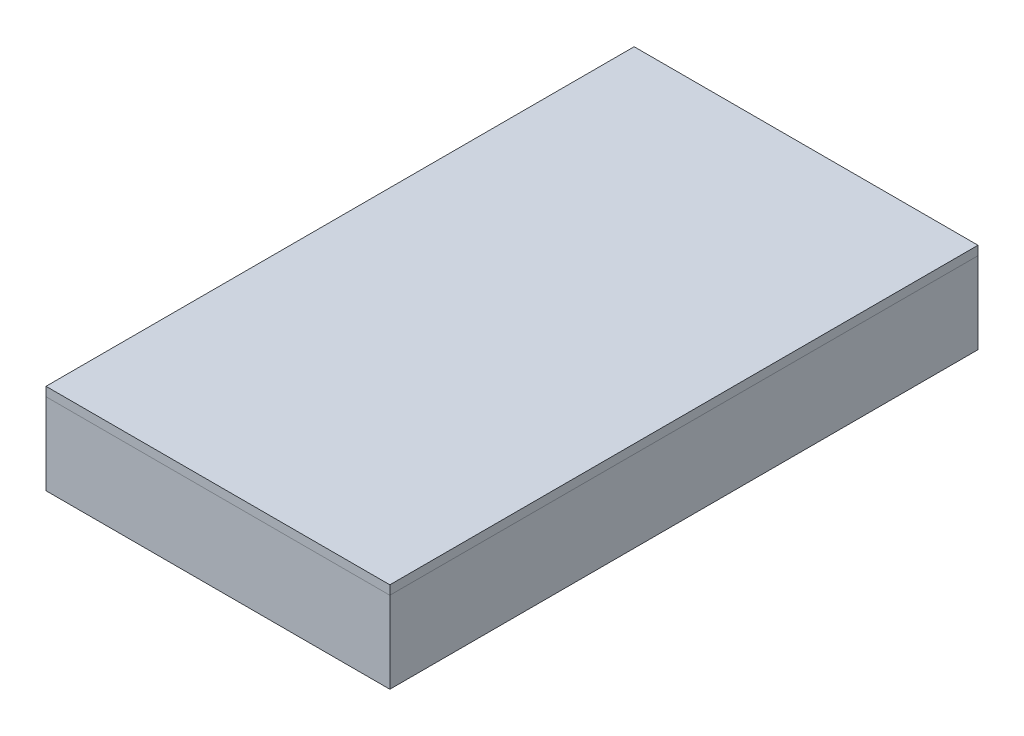
SolidWorks part; units mm, degrees
note: The reader was unsure of these and kept them because the rebuilt part matched: shared geometry of "Sketch3<3>", "Sketch6<3>", "Sketch6<4>".
ref_plane "Front Plane" through (0, 0, 0) normal (0, 0, 1) x (1, 0, 0)
ref_plane "Top Plane" through (0, 0, 0) normal (0, 1, 0) x (1, 0, 0)
ref_plane "Right Plane" through (0, 0, 0) normal (1, 0, 0) x (0, 0, -1)
sketch "Sketch2" plane through (0, 0, 0) normal (0, 1, 0) x (1, 0, 0)
  line L0 (9.3918, 23) -> (12.6392, 30.6504) construction
  line L1 (8.0012, 23) -> (11.3715, 30.9397) construction
  line L2 (-17.4418, -23.5727) -> (-14.5634, 23.4884) construction
  line L3 (14.5634, -23.4884) -> (17.4418, 23.5727) construction
  line L4 (-6.5783, 31) -> (10.4548, 31) construction
  line L5 (-10.4548, -31) -> (6.5783, -31) construction
  line L6 (-6.5783, 23) -> (9.3918, 23) construction
  line L7 (-9.3918, -23) -> (6.5783, -23) construction
  line L8 (-9.3918, -23) -> (-8.2297, -4) construction
  line L9 (9.3333, 22.0431) -> (12.9414, 30.5435) construction
  line L10 (6.5783, -23) -> (9.2488, -30.5411) construction
  line L11 (6.5783, -23) -> (7.7404, -4) construction
  line L12 (-7.7404, 4) -> (8.2297, 4) construction
  line L13 (-8.2297, -4) -> (7.7404, -4) construction
  line L14 (-6.5783, 23) -> (-12.0598, 28.827) construction
  line L15 (8.2297, 4) -> (9.3918, 23) construction
  line L16 (5.2204, -23) -> (8.0078, -30.8713) construction
  line L17 (-7.7404, 4) -> (-6.5783, 23) construction
  line L18 (-9.3918, -23) -> (-18.0557, -31.1502) construction
  line L19 (-11.4496, 29.3459) -> (-5.48, 23) construction
  line L20 (-12.615, 28.2496) -> (-6.6454, 21.9037) construction
  line L21 (-14.9719, -29.3476) -> (-8.2242, -23) construction
  line L22 (-16.0682, -28.1822) -> (-9.3205, -21.8346) construction
  line L23 (6.6283, -22.1826) -> (9.5483, -30.4283) construction
  line L24 (-11.6, 0) -> (-6.2918, 4) construction
  line L25 (-11.6, 0) -> (-6.2918, -4) construction
  line L26 (11.6, 0) -> (6.2918, 4) construction
  line L27 (11.6, 0) -> (6.2918, -4) construction
  line L28 (-7.6819, 4.9559) -> (-12.9293, 1.0017) construction
  line L29 (-12.9293, 1.0017) -> (-15.8061, 3.1696) construction
  line L30 (-16.2126, -3.4758) -> (-12.9293, -1.0017) construction
  line L31 (-12.9293, -1.0017) -> (-8.2615, -4.5192) construction
  line L32 (7.6819, -4.9559) -> (12.9293, -1.0017) construction
  line L33 (12.9293, -1.0017) -> (15.8061, -3.1696) construction
  line L34 (8.2615, 4.5192) -> (12.9293, 1.0017) construction
  line L35 (12.9293, 1.0017) -> (16.2126, 3.4758) construction
  line L36 (-19, -32.5) -> (-19, 32.5) construction
  line L37 (19, -32.5) -> (19, 32.5) construction
  line L38 (-19, 32.5) -> (19, 32.5) construction
  line L39 (-19, -32.5) -> (19, -32.5) construction
  line L40 (-16.8257, -13.5) -> (15.1743, -13.5) construction
  line L41 (-15.1743, 13.5) -> (16.8257, 13.5) construction
  line L42 (16.7794, 27) -> (-13.5065, 27) construction
  line L43 (-10.4548, -31) -> (13.8794, -31) construction
  line L44 (13.5065, -27) -> (-16.7794, -27) construction
  line L45 (10.1479, -30.1595) -> (13.8353, 30.1296) construction
  line L46 (-10.1479, 30.1595) -> (-13.8353, -30.1296) construction
  line L47 (-1.896, -31) -> (1.896, 31) construction
  arc A0 (-6.5783, 31) -> (-14.5634, 23.4884) centre (-6.5783, 23) ccw construction
  arc A1 (14.5634, -23.4884) -> (6.5783, -31) centre (6.5783, -23) cw construction
  arc A2 (17.4418, 23.5727) -> (10.4548, 31) centre (10.4548, 24) ccw construction
  arc A3 (-10.4548, -31) -> (-17.4418, -23.5727) centre (-10.4548, -24) cw construction
  point P0 (-16, 0)
  point P3 (-16, 0)
  point P8 (16, 0)
  point P42 (-11.6, 0)
  point P43 (11.6, 0)
  point P67 (7.1594, -13.5)
  point P70 (-7.1594, 13.5)
  point P72 (1.9383, 31)
  point P85 (1.6364, 27)
  point P86 (-12.8182, -13.5)
  point P87 (-11.1668, 13.5)
  point P88 (-1.6364, -27)
  point P89 (12.8182, 13.5)
  point P90 (11.1668, -13.5)
  dimension "D6" = 8
  dimension "D8" = 7
  dimension "D3" = 86.5
  dimension "D5" = 16
  dimension "D4" = 16
  dimension "D7" = 8
  dimension "D11" = 0.8
  dimension "D12" = 0.8
  dimension "D13" = 0.8
  dimension "D14" = 0.8
  dimension "D9" = 4
  dimension "D10" = 4
  dimension "D2" = 31
  dimension "D15" = 31
  dimension "D16" = 113
  dimension "D17" = 1.6
  dimension "D18" = 0.32
  dimension "D19" = 109.5
  dimension "D20" = 1.6
  dimension "D21" = 0.32
  dimension "D22" = 4.4
  dimension "D23" = 143
  dimension "D24" = 4.4
  dimension "D25" = 143
  dimension "D26" = 1.6
  dimension "D27" = 1.6
  dimension "D28" = 1.6
  dimension "D29" = 1.6
  dimension "D32" = 1.5
  dimension "D33" = 1.5
  dimension "D34" = 4
  dimension "D35" = 4
  dimension "D36" = 4
  dimension "D37" = 4
  dimension "D30" = 19
  dimension "D31" = 19
sketch "Sketch3" plane through (0, 0, 0) normal (0, 1, 0) x (1, 0, 0)
  line L0 (-15.8061, 3.1696) -> (-14.5634, 23.4884)
  line L1 (-15.8061, 3.1696) -> (-12.9293, 1.0017)
  line L2 (-12.9293, 1.0017) -> (-7.6819, 4.9559)
  line L3 (-7.6819, 4.9559) -> (-6.6454, 21.9037)
  line L4 (-6.6454, 21.9037) -> (-12.615, 28.2496)
  line L5 (-11.4496, 29.3459) -> (-5.48, 23)
  line L6 (-5.48, 23) -> (8.0012, 23)
  line L7 (8.0012, 23) -> (11.3715, 30.9397)
  line L8 (-6.5783, 31) -> (10.4548, 31)
  line L9 (-11.6, 0) -> (-6.2918, 4)
  line L10 (-6.2918, 4) -> (6.2918, 4)
  line L11 (6.2918, 4) -> (11.6, 0)
  line L12 (11.6, 0) -> (6.2918, -4)
  line L13 (6.2918, -4) -> (-6.2918, -4)
  line L14 (-6.2918, -4) -> (-11.6, 0)
  line L15 (9.3333, 22.0431) -> (12.9414, 30.5435)
  line L16 (9.3333, 22.0431) -> (8.2615, 4.5192)
  line L17 (8.2615, 4.5192) -> (12.9293, 1.0017)
  line L18 (12.9293, 1.0017) -> (16.2126, 3.4758)
  line L19 (16.2126, 3.4758) -> (17.4418, 23.5727)
  line L20 (6.6283, -22.1826) -> (7.6819, -4.9559)
  line L21 (7.6819, -4.9559) -> (12.9293, -1.0017)
  line L22 (12.9293, -1.0017) -> (15.8061, -3.1696)
  line L23 (15.8061, -3.1696) -> (14.5634, -23.4884)
  line L24 (6.6283, -22.1826) -> (9.5483, -30.4283)
  line L25 (8.0078, -30.8713) -> (5.2204, -23)
  line L26 (5.2204, -23) -> (-8.2242, -23)
  line L27 (-8.2242, -23) -> (-14.9719, -29.3476)
  line L28 (-16.0682, -28.1822) -> (-9.3205, -21.8346)
  line L29 (-9.3205, -21.8346) -> (-8.2615, -4.5192)
  line L30 (-8.2615, -4.5192) -> (-12.9293, -1.0017)
  line L31 (-12.9293, -1.0017) -> (-16.2126, -3.4758)
  line L32 (-16.2126, -3.4758) -> (-17.4418, -23.5727)
  line L33 (-10.4548, -31) -> (6.5783, -31)
  line L34 (-19, 32.5) -> (19, 32.5)
  line L35 (19, 32.5) -> (19, -32.5)
  line L36 (19, -32.5) -> (-19, -32.5)
  line L37 (-19, -32.5) -> (-19, 32.5)
  arc A0 (-14.5634, 23.4884) -> (-12.615, 28.2496) centre (-6.5783, 23) cw
  arc A1 (-11.4496, 29.3459) -> (-6.5783, 31) centre (-6.5783, 23) cw
  arc A2 (10.4548, 31) -> (11.3715, 30.9397) centre (10.4548, 24) cw
  arc A3 (12.9414, 30.5435) -> (17.4418, 23.5727) centre (10.4548, 24) cw
  arc A5 (9.5483, -30.4283) -> (14.5634, -23.4884) centre (6.5783, -23) ccw
  arc A6 (8.0078, -30.8713) -> (6.5783, -31) centre (6.5783, -23) cw
  arc A7 (-10.4548, -31) -> (-14.9719, -29.3476) centre (-10.4548, -24) cw
  arc A8 (-16.0682, -28.1822) -> (-17.4418, -23.5727) centre (-10.4548, -24) cw
extrude "Boss-Extrude1" add sketch "Sketch3" against normal blind 0.64 contours L37 L36 L35 L34 A5 L24 L20 L21 L22 L23 L13 L14 L9 L10 L11 L12 L0 A0 L4 L3 L2 L1 L8 A2 L7 L6 L5 A1 L15 A3 L19 L18 L17 L16 L33 A7 L27 L26 L25 A6 L28 A8 L32 L31 | A0 L0 L1 L2 L3 L4 | A2 L8 A1 L5 L6 L7 | A3 L15 L16 L17 L18 L19 | L14 L13 L12 L11 L10 L9 | A8 L28 L29 L30 L31 L32 | A7 L33 A6 L25 L26 L27 | L24 A5 L23 L22 L21 L20
extrude "Boss-Extrude2" add sketch "Sketch3<3>" against normal blind 10
sketch "Sketch3<3>" plane through (0, 0, 0) normal (0, 1, 0) x (1, 0, 0) same geometry as "Sketch3"
ref_plane "Plane1" through (0, -1, 0) normal (0, 1, 0) x (1, 0, 0)
split "Split1" trim tools "Plane1" bodies to split 110 resulting bodies 112 113
sketch "Sketch6" plane through (0, 0, 0) normal (0, 1, 0) x (1, 0, 0)
  line L0 (9.3918, 23) -> (8.2297, 4) construction
  line L1 (9.3918, 23) -> (-6.5783, 23) construction
  line L2 (0, -1000) -> (0, 1000) construction
  line L3 (-15.1743, 13.5) -> (16.8257, 13.5) construction
  line L4 (-16.8257, -13.5) -> (15.1743, -13.5) construction
  line L5 (8.2297, 4) -> (-7.7404, 4) construction
  line L6 (-6.5783, 23) -> (-7.7404, 4) construction
  line L7 (7.7404, -4) -> (6.5783, -23) construction
  line L8 (7.7404, -4) -> (-8.2297, -4) construction
  line L9 (6.5783, -23) -> (-9.3918, -23) construction
  line L10 (-8.2297, -4) -> (-9.3918, -23) construction
  line L11 (5.8269, -5.8) -> (-6.5364, -5.8)
  line L12 (-6.5364, -5.8) -> (-7.4783, -21.2)
  line L13 (4.885, -21.2) -> (-7.4783, -21.2)
  line L14 (5.8269, -5.8) -> (4.885, -21.2)
  line L15 (-4.885, 21.2) -> (-5.8269, 5.8)
  line L16 (6.5364, 5.8) -> (-5.8269, 5.8)
  line L17 (7.4783, 21.2) -> (6.5364, 5.8)
  line L18 (7.4783, 21.2) -> (-4.885, 21.2)
  circle A0 centre (0, 13.5) radius 1.5
  circle A1 centre (0, -13.5) radius 1.5
  circle A2 centre (0, 13.5) radius 1.6
  circle A3 centre (0, -13.5) radius 1.6
  point P19 (0, 0)
  dimension "D1" = 3
  dimension "D2" = 0.1
  dimension "D3" = 1.8
  dimension "D4" = 1.8
  dimension "D5" = 19
extrude "Boss-Extrude3" add sketch "Sketch6" against normal blind 3 contours A0 | A1
extrude "Cut-Extrude2" cut sketch "Sketch6<3>" against normal blind 4 contours A0 | A2 A0 | A1 | A3 A1
sketch "Sketch6<3>" plane through (0, 0, 0) normal (0, 1, 0) x (1, 0, 0) same geometry as "Sketch6"
sketch "Sketch4" plane through (0, 0, 0) normal (0, 1, 0) x (1, 0, 0)
  line L1 (-4.8561, 29.5) -> (0.1439, 29.5)
  line L2 (-4.8561, 29.5) -> (-4.8561, 24.5)
  line L3 (-4.8561, 24.5) -> (0.1439, 24.5)
  line L4 (0.1439, 29.5) -> (0.1439, 24.5)
  line L5 (-4.8561, 29.5) -> (0.1439, 24.5) construction
  line L6 (-4.8561, 24.5) -> (0.1439, 29.5) construction
  line L7 (10.5629, 20) -> (15.5629, 20)
  line L8 (10.5629, 20) -> (10.5629, 15)
  line L9 (10.5629, 15) -> (15.5629, 15)
  line L10 (15.5629, 20) -> (15.5629, 15)
  line L11 (10.5629, 20) -> (15.5629, 15) construction
  line L12 (10.5629, 15) -> (15.5629, 20) construction
  line L13 (-6.5075, 2.5) -> (-1.5075, 2.5)
  line L14 (-6.5075, 2.5) -> (-6.5075, -2.5)
  line L15 (-6.5075, -2.5) -> (-1.5075, -2.5)
  line L16 (-1.5075, 2.5) -> (-1.5075, -2.5)
  line L17 (-6.5075, 2.5) -> (-1.5075, -2.5) construction
  line L18 (-6.5075, -2.5) -> (-1.5075, 2.5) construction
  line L19 (-13.4222, 20) -> (-8.4222, 20)
  line L20 (-13.4222, 20) -> (-13.4222, 15)
  line L21 (-13.4222, 15) -> (-8.4222, 15)
  line L22 (-8.4222, 20) -> (-8.4222, 15)
  line L23 (-13.4222, 20) -> (-8.4222, 15) construction
  line L24 (-13.4222, 15) -> (-8.4222, 20) construction
  line L25 (-15.0736, -7) -> (-10.0736, -7)
  line L26 (-15.0736, -7) -> (-15.0736, -12)
  line L27 (-15.0736, -12) -> (-10.0736, -12)
  line L28 (-10.0736, -7) -> (-10.0736, -12)
  line L29 (-15.0736, -7) -> (-10.0736, -12) construction
  line L30 (-15.0736, -12) -> (-10.0736, -7) construction
  line L31 (-8.1589, -29.5) -> (-3.1589, -29.5)
  line L32 (-8.1589, -29.5) -> (-8.1589, -24.5)
  line L33 (-8.1589, -24.5) -> (-3.1589, -24.5)
  line L34 (-3.1589, -29.5) -> (-3.1589, -24.5)
  line L35 (-8.1589, -29.5) -> (-3.1589, -24.5) construction
  line L36 (-8.1589, -24.5) -> (-3.1589, -29.5) construction
  line L37 (8.9115, -12) -> (13.9115, -12)
  line L38 (8.9115, -12) -> (8.9115, -7)
  line L39 (8.9115, -7) -> (13.9115, -7)
  line L40 (13.9115, -12) -> (13.9115, -7)
  line L41 (8.9115, -12) -> (13.9115, -7) construction
  line L42 (8.9115, -7) -> (13.9115, -12) construction
  line L44 (2.0965, -31.2442) -> (5.8886, 30.7558)
  line L45 (2.0965, -31.2442) -> (5.8886, 30.7558) construction
  line L46 (-5.8886, -30.7558) -> (-2.0965, 31.2442)
  line L47 (-5.8886, -30.7558) -> (-2.0965, 31.2442) construction
  line L49 (-15.1743, 9.5) -> (16.8257, 9.5)
  line L50 (-15.1743, 9.5) -> (16.8257, 9.5) construction
  line L51 (-15.1743, 17.5) -> (16.8257, 17.5)
  line L52 (-15.1743, 17.5) -> (16.8257, 17.5) construction
  line L53 (16.7794, 27) -> (-13.5065, 27) construction
  line L54 (-16.8257, -17.5) -> (15.1743, -17.5)
  line L55 (-16.8257, -17.5) -> (15.1743, -17.5) construction
  line L56 (-16.8257, -9.5) -> (15.1743, -9.5)
  line L57 (-16.8257, -9.5) -> (15.1743, -9.5) construction
  line L58 (10.1479, -30.1595) -> (13.8353, 30.1296) construction
  line L59 (13.5065, -27) -> (-16.7794, -27) construction
  line L60 (-10.1479, 30.1595) -> (-13.8353, -30.1296) construction
  line L61 (-0.1439, -29.5) -> (4.8561, -29.5)
  line L62 (-0.1439, -29.5) -> (-0.1439, -24.5)
  line L63 (-0.1439, -24.5) -> (4.8561, -24.5)
  line L64 (4.8561, -29.5) -> (4.8561, -24.5)
  line L65 (-0.1439, -29.5) -> (4.8561, -24.5) construction
  line L66 (-0.1439, -24.5) -> (4.8561, -29.5) construction
  line L67 (1.5075, 2.5) -> (6.5075, 2.5)
  line L68 (1.5075, 2.5) -> (1.5075, -2.5)
  line L69 (1.5075, -2.5) -> (6.5075, -2.5)
  line L70 (6.5075, 2.5) -> (6.5075, -2.5)
  line L71 (1.5075, 2.5) -> (6.5075, -2.5) construction
  line L72 (1.5075, -2.5) -> (6.5075, 2.5) construction
  line L73 (3.1589, 29.5) -> (8.1589, 29.5)
  line L74 (3.1589, 29.5) -> (3.1589, 24.5)
  line L75 (3.1589, 24.5) -> (8.1589, 24.5)
  line L76 (8.1589, 29.5) -> (8.1589, 24.5)
  line L77 (3.1589, 29.5) -> (8.1589, 24.5) construction
  line L78 (3.1589, 24.5) -> (8.1589, 29.5) construction
  line L79 (10.0736, 12) -> (15.0736, 12)
  line L80 (10.0736, 12) -> (10.0736, 7)
  line L81 (10.0736, 7) -> (15.0736, 7)
  line L82 (15.0736, 12) -> (15.0736, 7)
  line L83 (10.0736, 12) -> (15.0736, 7) construction
  line L84 (10.0736, 7) -> (15.0736, 12) construction
  line L85 (-13.9115, 12) -> (-8.9115, 12)
  line L86 (-13.9115, 12) -> (-13.9115, 7)
  line L87 (-13.9115, 7) -> (-8.9115, 7)
  line L88 (-8.9115, 12) -> (-8.9115, 7)
  line L89 (-13.9115, 12) -> (-8.9115, 7) construction
  line L90 (-13.9115, 7) -> (-8.9115, 12) construction
  line L91 (8.4222, -20) -> (13.4222, -20)
  line L92 (8.4222, -20) -> (8.4222, -15)
  line L93 (8.4222, -15) -> (13.4222, -15)
  line L94 (13.4222, -20) -> (13.4222, -15)
  line L95 (8.4222, -20) -> (13.4222, -15) construction
  line L96 (8.4222, -15) -> (13.4222, -20) construction
  line L97 (-15.5629, -15) -> (-10.5629, -15)
  line L98 (-15.5629, -15) -> (-15.5629, -20)
  line L99 (-15.5629, -20) -> (-10.5629, -20)
  line L100 (-10.5629, -15) -> (-10.5629, -20)
  line L101 (-15.5629, -15) -> (-10.5629, -20) construction
  line L102 (-15.5629, -20) -> (-10.5629, -15) construction
  point P0 (-2.3561, 27)
  point P5 (0, 0)
  point P6 (13.0629, 17.5)
  point P11 (-1.6364, 27)
  point P12 (-4.0075, 0)
  point P17 (0, 0)
  point P18 (-10.9222, 17.5)
  point P24 (-12.5736, -9.5)
  point P30 (-5.6589, -27)
  point P35 (2.9004, 17.5)
  point P36 (11.4115, -9.5)
  point P42 (0, 0)
  point P57 (0, 0)
  point P58 (0, 0)
  point P61 (0, 0)
  point P62 (0, 0)
  point P65 (0, 0)
  point P66 (0, 0)
  point P67 (0, 0)
  point P68 (0, 0)
  point P69 (0, 0)
  point P72 (0, 0)
  point P73 (0, 0)
  point P74 (0, 0)
  point P76 (0, 0)
  point P77 (0, 0)
  point P78 (2.3561, -27)
  point P83 (0, 0)
  point P84 (0, 0)
  point P85 (4.0075, 0)
  point P90 (0, 0)
  point P91 (0, 0)
  point P92 (5.6589, 27)
  point P97 (0, 0)
  point P98 (0, 0)
  point P99 (12.5736, 9.5)
  point P104 (0, 0)
  point P105 (0, 0)
  point P106 (0, 0)
  point P107 (0, 0)
  point P108 (-10.861, 18.5)
  point P109 (-11.4115, 9.5)
  point P114 (0, 0)
  point P115 (0, 0)
  point P116 (10.9222, -17.5)
  point P121 (0, 0)
  point P122 (0, 0)
  point P123 (-13.0629, -17.5)
  point P128 (0, 0)
  point P129 (0, 0)
  dimension "D1" = 5
  dimension "D2" = 27
  dimension "D3" = 27
  dimension "D4" = 17.5
  dimension "D5" = 9.5
  dimension "D6" = 9.5
  dimension "D7" = 1.6514
  dimension "D8" = 17.5
  dimension "D9" = 15.419
  dimension "D10" = 8.5661
  dimension "D11" = 5.6589
  dimension "D18" = 4.0075
  dimension "D19" = 2.3561
  dimension "D20" = 5.6589
  dimension "D21" = 13.0629
  dimension "D22" = 12.5736
  dimension "D23" = 10.9222
  dimension "D24" = 11.4115
  dimension "D25" = 2.3561
  dimension "D26" = 5.6589
  dimension "D27" = 11.4115
  dimension "D28" = 10.9222
  dimension "D29" = 12.5736
  dimension "D30" = 13.0629
  dimension "D12" = 4
  dimension "D13" = 4
  dimension "D14" = 4
  dimension "D15" = 4
  dimension "D16" = 4
  dimension "D17" = 4
sketch "Sketch5" plane through (0, 0, 0) normal (0, 1, 0) x (1, 0, 0)
  line L0 (-19, 32.5) -> (19, 32.5) construction
  line L1 (-19, -32.5) -> (-19, 32.5) construction
  line L2 (19, -32.5) -> (19, 32.5) construction
  line L3 (-19, -32.5) -> (19, -32.5) construction
  circle A0 centre (-16, 29.5) radius 1.45
  circle A1 centre (16, -29.5) radius 1.45
  dimension "D1" = 2.9
  dimension "D4" = 3
  dimension "D5" = 3
  dimension "D6" = 16
  dimension "D7" = 29.5
  dimension "D8" = 29.5
  dimension "D9" = 16
extrude "Cut-Extrude1" cut sketch "Sketch5" along normal blind 6 from surface at -10 starting at face at (-13.4404, -10, 13.7846)
extrude "Cut-Extrude3" cut sketch "Sketch6<4>" along normal blind 5 from surface at -10 contours L17 L18 L15 L16 A2 | A0 | A2 A0 | L14 L11 L12 L13 A3 | A1 | A3 A1 starting at face at (-16, -10, -30.95)
sketch "Sketch6<4>" plane through (0, 0, 0) normal (0, 1, 0) x (1, 0, 0) same geometry as "Sketch6"
equation "\"D4@Sketch2\"=\"D5@Sketch2\""
equation "\"D7@Sketch2\"=\"D6@Sketch2\""
equation "\"D11@Sketch2\"=\"D6@Sketch2\"/10"
equation "\"D12@Sketch2\"=\"D11@Sketch2\""
equation "\"D13@Sketch2\"=\"D11@Sketch2\""
equation "\"D14@Sketch2\"=\"D13@Sketch2\""
equation "\"D9@Sketch2\"=\"D6@Sketch2\"/2"
equation "\"D10@Sketch2\"=\"D9@Sketch2\""
equation "\"D15@Sketch2\"=\"D2@Sketch2\""
equation "\"D17@Sketch2\"=\"D12@Sketch2\"*2"
equation "\"D18@Sketch2\"=\"D17@Sketch2\"/5"
equation "\"D19@Sketch2\"=\"D16@Sketch2\"-(90-\"D3@Sketch2\")"
equation "\"D20@Sketch2\"=\"D17@Sketch2\""
equation "\"D21@Sketch2\"=\"D18@Sketch2\""
equation "\"D22@Sketch2\"=\"D6@Sketch2\"*0.55"
equation "\"D24@Sketch2\"=\"D22@Sketch2\""
equation "\"D25@Sketch2\"=\"D23@Sketch2\""
equation "\"D26@Sketch2\"=\"D17@Sketch2\""
equation "\"D27@Sketch2\"=\"D26@Sketch2\""
equation "\"D28@Sketch2\"=\"D27@Sketch2\""
equation "\"D29@Sketch2\"=\"D28@Sketch2\""
equation "\"D33@Sketch2\"=\"D32@Sketch2\""
equation "\"D34@Sketch2\"=\"D6@Sketch2\"/2"
equation "\"D35@Sketch2\"=\"D34@Sketch2\""
equation "\"D36@Sketch2\"=\"D34@Sketch2\""
equation "\"D37@Sketch2\"=\"D34@Sketch2\""
equation "\"D31@Sketch2\"=\"D30@Sketch2\""
equation "\"D3@Sketch5\"=\"D2@Sketch5\""
equation "\"D4@Sketch5\"=\"D2@Sketch5\""
equation "\"D5@Sketch5\"=\"D4@Sketch5\""
